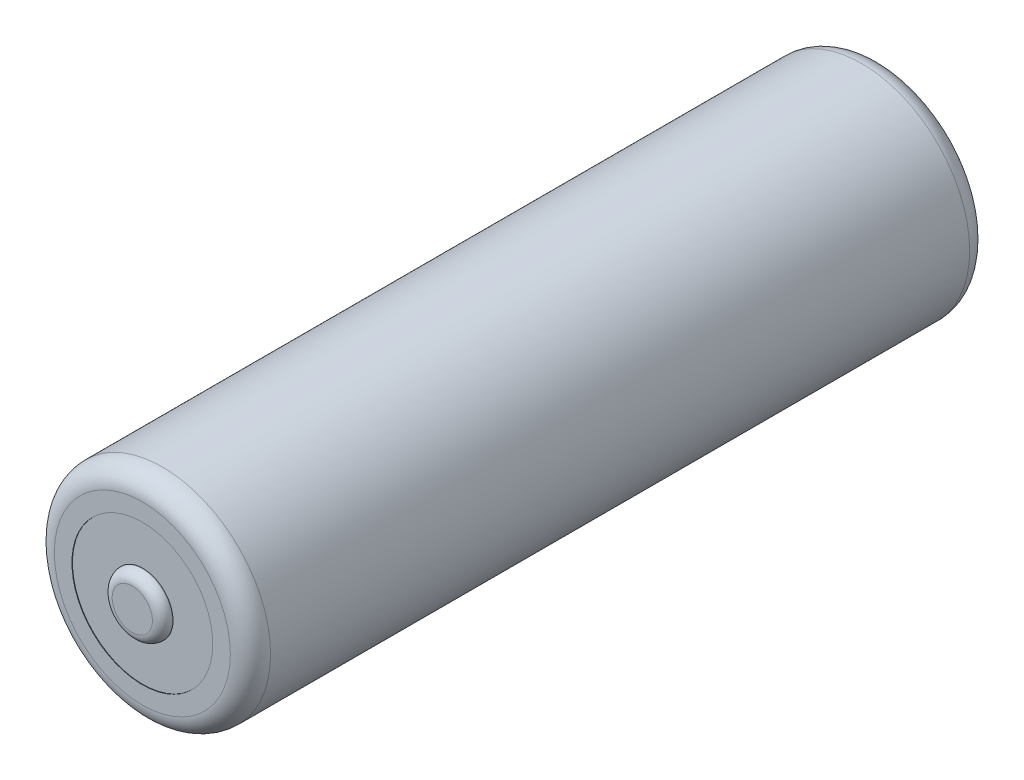
SolidWorks part; units mm, degrees
ref_plane "Front Plane" through (0, 0, 0) normal (0, 0, 1) x (1, 0, 0)
ref_plane "Top Plane" through (0, 0, 0) normal (0, 1, 0) x (1, 0, 0)
ref_plane "Right Plane" through (0, 0, 0) normal (1, 0, 0) x (0, 0, -1)
sketch "Sketch1" plane through (0, 0, 0) normal (0, 0, 1) x (1, 0, 0)
  circle A0 centre (0, 0) radius 10.75
  dimension "D1" = 21.5
extrude "Boss-Extrude1" add sketch "Sketch1" along normal blind 73.5 contours A0
sketch "Sketch2" plane through (0, 0, 73.5) normal (0, 0, 1) x (1, 0, 0)
  circle A0 centre (0, 0) radius 3
  circle A1 centre (0, 0) radius 7
extrude "Boss-Extrude2" add sketch "Sketch2" along normal blind 1 contours A0 region at (0, 0, 73.5)
extrude "Cut-Extrude1" cut sketch "Sketch2<3>" against normal blind 0.05
sketch "Sketch2<3>" plane through (0, 0, 73.5) normal (0, 0, 1) x (1, 0, 0) same geometry as "Sketch2"
sketch "Sketch3" plane through (0, 0, 0) normal (0, 0, -1) x (-1, 0, 0)
  circle A0 centre (0, 0) radius 7.5
extrude "Cut-Extrude2" cut sketch "Sketch3" against normal blind 0.05
fillet "Fillet1" radius 2 2 edges at (10.75, 0, 73.5) (10.75, 0, 0)
fillet "Fillet2" radius 1 1 edges at (3, 0, 74.5)
